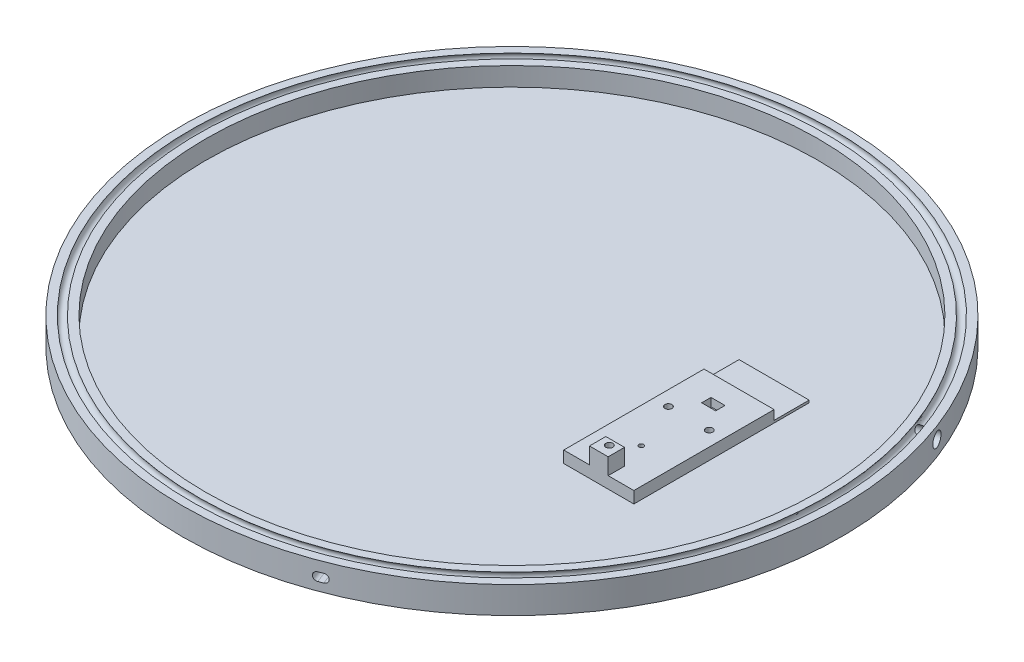
SolidWorks part; units mm, degrees
ref_plane "Front Plane" through (0, 0, 0) normal (0, 0, 1) x (1, 0, 0)
ref_plane "Top Plane" through (0, 0, 0) normal (0, 1, 0) x (1, 0, 0)
ref_plane "Right Plane" through (0, 0, 0) normal (1, 0, 0) x (0, 0, -1)
sketch "Sketch1" plane through (0, 0, 0) normal (0, 1, 0) x (1, 0, 0)
  circle A0 centre (0, 0) radius 141
  dimension "D1" = 282
extrude "Boss-Extrude1" add sketch "Sketch1" along normal blind 3.5
sketch "Sketch2" plane through (0, 3.5, 0) normal (0, 1, 0) x (1, 0, 0)
  circle A0 centre (0, 0) radius 131
  circle A1 centre (0, 0) radius 141
  dimension "D1" = 262
extrude "Boss-Extrude2" add sketch "Sketch2" along normal blind 8
sketch "Sketch3" plane through (0, 11.5, 0) normal (0, 1, 0) x (1, 0, 0)
  circle A0 centre (0, 0) radius 136
  dimension "D1" = 272
sketch "Sketch4" plane through (0, 3.5, 0) normal (0, 1, 0) x (1, 0, 0)
  line L0 (0, 0) -> (46.4876, -122.4741)
  circle A0 centre (0, 0) radius 131 construction
  point P5 (47.745, -121.9894)
  point P6 (46.4876, -122.4741)
ref_plane "Plane1" through (0, 0, 0) normal (-0.9349, 0, 0.3549) x (0.3549, 0, 0.9349)
sketch "Sketch5" plane through (0, 0, 0) normal (-0.9349, 0, 0.3549) x (0.3549, 0, 0.9349)
  line L6 (136, 11.5) -> (-136, 11.5) construction
  circle A0 centre (136, 10.2) radius 2
  dimension "D1" = 4
  dimension "D2" = 1.3
  dimension "D3" = 136
sweep "Cut-Sweep1" cut profiles "Sketch5" path "Sketch3"
ref_plane "Plane3" through (46.4876, 0, 122.4741) normal (-0.3549, 0, -0.9349) x (-0.9349, 0, 0.3549)
sketch "Sketch6" plane through (46.4876, 0, 122.4741) normal (-0.3549, 0, -0.9349) x (-0.9349, 0, 0.3549)
  line L1 (1, 5.3991) -> (-1, 5.3991) construction
  line L2 (1, 3.5991) -> (-1, 3.5991)
  line L3 (1, 7.1991) -> (-1, 7.1991)
  arc A1 (1, 3.5991) -> (1, 7.1991) centre (1, 5.3991) ccw
  arc A2 (-1, 7.1991) -> (-1, 3.5991) centre (-1, 5.3991) ccw
  point P6 (0, 5.3991)
  dimension "D1" = 2
  dimension "D2" = 1.8
extrude "Cut-Extrude3" cut sketch "Sketch6" against normal blind 15 and the other way blind 5 contours L3 A2 L2 A1
sketch "Sketch7" plane through (0, 3.5, 0) normal (0, 1, 0) x (1, 0, 0)
  line L1 (87.9173, -35.7518) -> (57.9173, -35.7518)
  line L2 (87.9173, -35.7518) -> (87.9173, 39.2482)
  line L3 (87.9173, 39.2482) -> (57.9173, 39.2482)
  line L4 (57.9173, -35.7518) -> (57.9173, 39.2482)
  circle A0 centre (72.9173, -17.5518) radius 1
  point P4 (3.8588, 74.9007)
  point P5 (74.6364, 7.376)
  point P6 (74.6627, 7.1053)
  point P7 (0, 0)
  point P8 (0, 0)
  point P9 (26.3172, -70.2311)
  point P10 (0, 0)
  point P11 (72.9173, -17.5518)
  dimension "D3" = 18.2
  dimension "D4" = 15
  dimension "D5" = 2
  dimension "D1" = 75
  dimension "D2" = 30
  dimension "D6" = 75
extrude "Boss-Extrude3" add sketch "Sketch7" along normal blind 5
sketch "Sketch8" plane through (0, 8.5, 0) normal (0, 1, 0) x (1, 0, 0)
  line L0 (57.9173, -35.7518) -> (87.9173, -35.7518) construction
  line L1 (68.9173, -35.7518) -> (76.9173, -35.7518)
  line L2 (68.9173, -35.7518) -> (68.9173, -28.7518)
  line L3 (68.9173, -28.7518) -> (76.9173, -28.7518)
  line L4 (76.9173, -35.7518) -> (76.9173, -28.7518)
  line L5 (57.9173, 39.2482) -> (57.9173, -35.7518) construction
  line L6 (87.9173, -35.7518) -> (87.9173, 39.2482) construction
  dimension "D1" = 11
  dimension "D2" = 8
  dimension "D3" = 11
  dimension "D4" = 7
extrude "Boss-Extrude4" add sketch "Sketch8" along normal blind 7
sketch "Sketch9" plane through (0, 8.5, 0) normal (0, 1, 0) x (1, 0, 0)
  line L0 (76.9173, -28.7518) -> (68.9173, -28.7518) construction
  line L1 (69.9173, 11.2482) -> (75.9173, 11.2482)
  line L2 (69.9173, 11.2482) -> (69.9173, 15.2482)
  line L3 (69.9173, 15.2482) -> (75.9173, 15.2482)
  line L4 (75.9173, 11.2482) -> (75.9173, 15.2482)
  line L5 (57.9173, 39.2482) -> (57.9173, -35.7518) construction
  line L6 (87.9173, -35.7518) -> (87.9173, 39.2482) construction
  dimension "D1" = 40
  dimension "D2" = 4
  dimension "D3" = 6
  dimension "D4" = 12
  dimension "D5" = 12
extrude "Cut-Extrude6" cut sketch "Sketch9" against normal blind 3.5
sketch "Sketch10" plane through (0, 8.5, 0) normal (0, 1, 0) x (1, 0, 0)
  line L0 (87.9173, 39.2482) -> (57.9173, 39.2482) construction
  line L1 (57.9173, 39.2482) -> (87.9173, 39.2482)
  line L2 (57.9173, 39.2482) -> (57.9173, 24.2482)
  line L3 (57.9173, 24.2482) -> (87.9173, 24.2482)
  line L4 (87.9173, 39.2482) -> (87.9173, 24.2482)
  line L5 (57.9173, 39.2482) -> (57.9173, -35.7518) construction
  line L6 (87.9173, -35.7518) -> (87.9173, 39.2482) construction
  point P10 (53.689, -15.3074)
  point P11 (0, 0)
  point P12 (53.689, -18.5308)
  point P13 (59.6627, 48.4225)
  dimension "D1" = 15
hole_wizard "Ø3.0mm Dowel Hole2" positions "Sketch11" profile "Sketch12" hole size "Ø3.0" standard "GB"
sketch "Sketch11" plane through (0, 15.5, 0) normal (0, 1, 0) x (1, 0, 0)
  line L0 (68.9173, -28.7518) -> (68.9173, -35.7518) construction
  line L1 (76.9173, -35.7518) -> (76.9173, -28.7518) construction
  line L2 (76.9173, -28.7518) -> (68.9173, -28.7518) construction
  point P0 (72.9173, -31.2518)
  dimension "D1" = 4
  dimension "D2" = 4
  dimension "D3" = 2.5
sketch "Sketch12" plane through (72.9173, 15.5, 31.2518) normal (1, 0, 0) x (0, 0, 1)
  line L0 (0, 0) -> (0, 10.9013)
  line L1 (0, 10.9013) -> (1.5, 10)
  line L2 (1.5, 10) -> (1.5, 0)
  line L5 (1.5, 0) -> (0, 0)
  line L10 (0, 10.9013) -> (-1.5, 10) construction
  line L11 (0, -6.35) -> (0, 107.95) construction
  dimension "Hole Dia." = 3
  dimension "Hole Depth" = 10
  dimension "Drill Angle" = 118
hole_wizard "Ø3.0mm Dowel Hole3" positions "3DSketch1" profile "Sketch13" hole size "Ø3.0" standard "GB"
sketch3d "3DSketch1"
  line L0 (76.9173, 8.5, 28.7518) -> (68.9173, 8.5, 28.7518) construction
  line L1 (57.9173, 8.5, -39.2482) -> (57.9173, 8.5, 35.7518) construction
  line L2 (87.9173, 8.5, 35.7518) -> (87.9173, 8.5, -39.2482) construction
  point P0 (64.1673, 8.5, -2.7482)
  point P2 (81.6673, 8.5, -2.7482)
  dimension "D1" = 31.5
  dimension "D2" = 31.5
  dimension "D3" = 17.5
  dimension "D4" = 6.25
  dimension "D5" = 6.25
sketch "Sketch13" plane through (64.1673, 8.5, -2.7482) normal (1, 0, 0) x (0, 0, 1)
  line L0 (0, 0) -> (0, 5.9013)
  line L1 (0, 5.9013) -> (1.5, 5)
  line L2 (1.5, 5) -> (1.5, 0)
  line L5 (1.5, 0) -> (0, 0)
  line L10 (0, 5.9013) -> (-1.5, 5) construction
  line L11 (0, -6.35) -> (0, 107.95) construction
  dimension "Hole Dia." = 3
  dimension "Hole Depth" = 5
  dimension "Drill Angle" = 118
extrude "Cut-Extrude7" cut sketch "Sketch10" against normal blind 4
ref_plane "Plane4" through (131.8233, 0, -50.0362) normal (0.9349, 0, -0.3549) x (-0.3549, 0, -0.9349)
sketch "Sketch15" plane through (131.8233, 0, -50.0362) normal (0.9349, 0, -0.3549) x (-0.3549, 0, -0.9349)
  line L2 (131, 3.5) -> (-131, 3.5) construction
  circle A0 centre (0, 6.5) radius 3
  point P6 (1.9339, 4.0342)
  dimension "D2" = 6
  dimension "D1" = 3
extrude "Cut-Extrude9" cut sketch "Sketch15" against normal blind 15
ref_axis "Axis1" through (72.9173, 4.5987, 31.2518) along (-0.919, -0.0138, -0.3939)
equation "\"GeneralThickness\"= 3"
equation "\"D2\" = \"GeneralThickness\""
equation "\"BearBallRadio\"= 136"
equation "\"D1@Sketch1\"=\"BearBallRadio\"*2+10"
equation "\"D1@Sketch2\"=\"BearBallRadio\"*2-10"
equation "\"D1@Sketch3\"=\"BearBallRadio\"*2"
equation "\"BallDia\"=4"
equation "\"D1@Sketch5\"=\"BallDia\""
equation "\"D3@Sketch5\"=\"BearBallRadio\""
